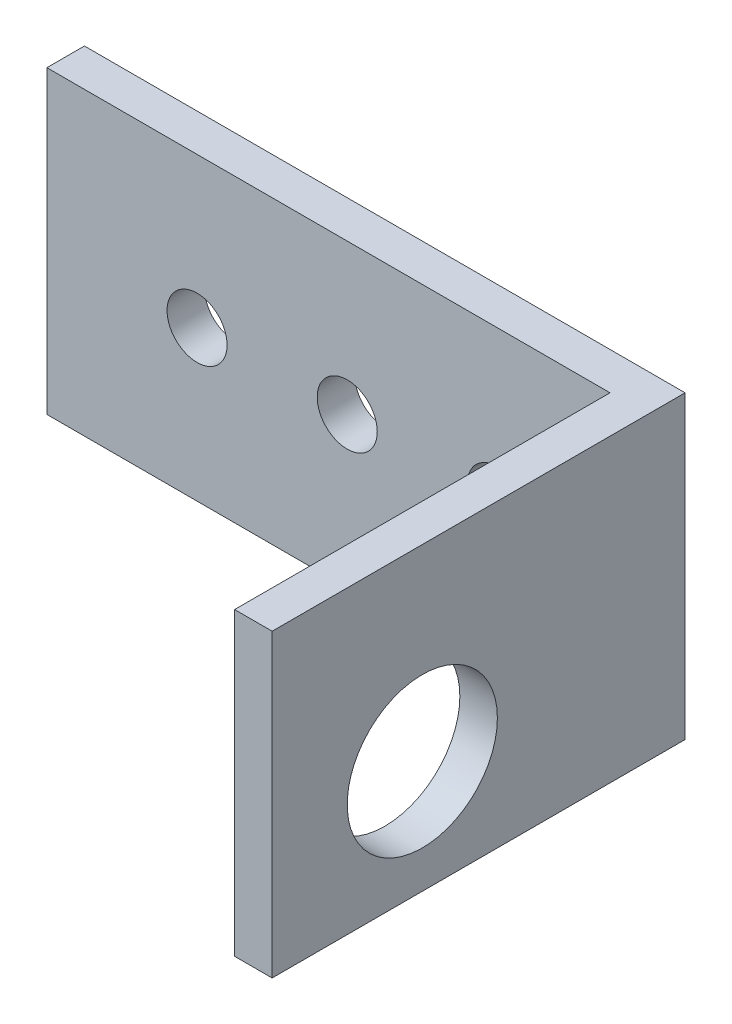
SolidWorks part; units mm, degrees
material "6061-T6 (SS)"
ref_plane "Front Plane" through (0, 0, 0) normal (0, 0, 1) x (1, 0, 0)
ref_plane "Top Plane" through (0, 0, 0) normal (0, 1, 0) x (1, 0, 0)
ref_plane "Right Plane" through (0, 0, 0) normal (1, 0, 0) x (0, 0, -1)
sketch "Sketch1" plane through (0, 0, 0) normal (0, 1, 0) x (1, 0, 0)
  line L1 (-25.4, -17.4625) -> (25.4, -17.4625)
  line L2 (-25.4, -17.4625) -> (-25.4, 17.4625)
  line L3 (-25.4, 17.4625) -> (25.4, 17.4625)
  line L4 (25.4, -17.4625) -> (25.4, 17.4625)
  line L5 (-25.4, -17.4625) -> (25.4, 17.4625) construction
  line L6 (-25.4, 17.4625) -> (25.4, -17.4625) construction
  line L7 (-25.4, -17.4625) -> (22.225, -17.4625)
  line L8 (-25.4, -17.4625) -> (-25.4, 14.2875)
  line L9 (-25.4, 14.2875) -> (22.225, 14.2875)
  line L10 (22.225, -17.4625) -> (22.225, 14.2875)
  point P0 (0, 0)
  dimension "D1" = 50.8
  dimension "D2" = 34.925
  dimension "D3" = 47.625
  dimension "D4" = 31.75
extrude "Boss-Extrude1" add sketch "Sketch1" along normal blind 25.4 contours L10 L1 L4 L3 L2 L9 region at (22.8415, 0, 1.5875)
sketch "Sketch2" plane through (25.4, 0, 0) normal (1, 0, 0) x (0, 0, -1)
  line L1 (-17.4625, 25.4) -> (-17.4625, 0) construction
  line L2 (-17.4625, 0) -> (17.4625, 0) construction
  circle A0 centre (-4.7625, 9.525) radius 6.35
  dimension "D1" = 12.7
  dimension "D2" = 9.525
  dimension "D3" = 12.7
extrude "Cut-Extrude1" cut sketch "Sketch2" against normal up to surface (3.175 mm away) up to face at (22.225, 12.7, 1.5875)
sketch "Sketch3" plane through (0, 0, -14.2875) normal (0, 0, 1) x (1, 0, 0)
  line L0 (-25.4, 25.4) -> (-25.4, 0) construction
  line L1 (-25.4, 0) -> (22.225, 0) construction
  circle A0 centre (-12.7, 12.7) radius 2.54
  circle A1 centre (0, 12.7) radius 2.54
  circle A2 centre (12.7, 12.7) radius 2.54
  point P6 (0, 0)
  dimension "D1" = 5.08
  dimension "D2" = 12.7
  dimension "D3" = 12.7
  dimension "D4" = 12.7
  dimension "D5" = 12.7
extrude "Cut-Extrude2" cut sketch "Sketch3" against normal up to surface (3.175 mm away) up to face at (0, 12.7, -17.4625)
